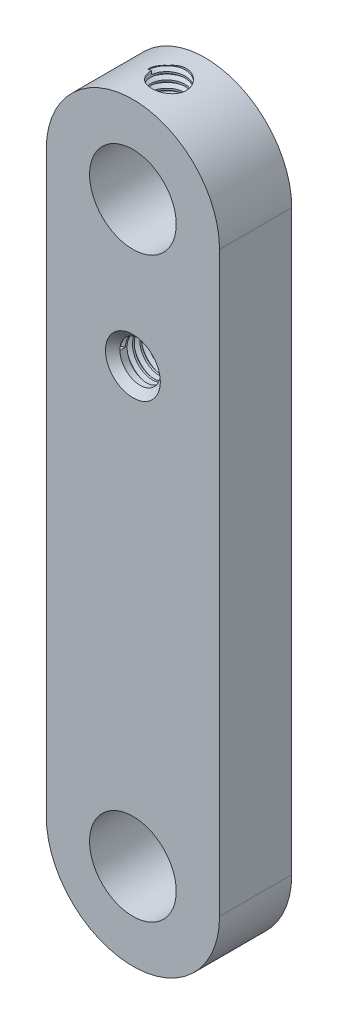
SolidWorks part; units mm, degrees
material "Stop 1060"
ref_plane "Płaszczyzna przednia" through (0, 0, 0) normal (0, 0, 1) x (1, 0, 0)
ref_plane "Płaszczyzna górna" through (0, 0, 0) normal (0, 1, 0) x (1, 0, 0)
ref_plane "Płaszczyzna prawa" through (0, 0, 0) normal (1, 0, 0) x (0, 0, -1)
sketch "Szkic1" plane through (0, 0, 0) normal (0, 0, 1) x (1, 0, 0)
  line L0 (0, 0) -> (0, -40)
  line L1 (6, -40) -> (6, 0)
  line L2 (-6, 0) -> (-6, -40)
  arc A1 (6, 0) -> (-6, 0) centre (0, 0) ccw
  circle A2 centre (0, -40) radius 3
  arc A3 (-6, -40) -> (6, -40) centre (0, -40) ccw
  circle A8 centre (0, -10) radius 1.4
  circle A9 centre (0, 0) radius 3
  dimension "D1" = 6
  dimension "D2" = 12
  dimension "D4" = 6
  dimension "D5" = 12
  dimension "D7" = 2.8
  dimension "D8" = 10
  dimension "D3" = 40
extrude "Dodanie-wyciągnięcie1" add sketch "Szkic1" along normal blind 5 contours L2 A3 L1 A1 A2 region at (0, -45.4663, 0)
chamfer "Sfazowanie1" distance 0.5 angle 45 2 edges at (1.4, -10, 0) (1.4, -10, 5)
thread "Gwint1" pitch 0.5 method cut profile "Profil gwintu1" start angle 0, offset 0, length 10, pitch 0.5, diameter 2.8
ref_plane "Płaszczyzna1" through (-1.4, -10, 4.5) normal (0, -1, 0) x (-1, 0, 0)
sketch "Profil gwintu1" plane through (-1.4, -10, 4.5) normal (0, -1, 0) x (-1, 0, 0)
  line L0 (0, 0) -> (0, 0.5) construction
  line L1 (0, 0) -> (0.2706, 0.1562)
  line L2 (0.2706, 0.1562) -> (0.2706, 0.2187)
  line L3 (0.2706, 0.2187) -> (0, 0.375)
  line L4 (0.2706, 0.1875) -> (0, 0.1875) construction
  line L11 (0, 0) -> (0, 0.375)
  point P2 (0, 0)
  dimension "Pitch" = 0.5
  dimension "Profile_Angle" = 60
  dimension "Profile_Land" = 0.0625
  dimension "Profile_Height" = 0.2706
ref_plane "Płaszczyzna2" through (0, 6, 0) normal (0, 1, 0) x (1, 0, 0)
sketch "Szkic4" plane through (0, 6, 0) normal (0, 1, 0) x (1, 0, 0)
  line L0 (6, -5) -> (6, 0) construction
  line L1 (6, 0) -> (-6, 0) construction
  circle A0 centre (0, -2.5) radius 1.2
  dimension "D1" = 6
  dimension "D2" = 2.5
  dimension "D3" = 2.4
extrude "Wytnij-wyciągnięcie1" cut sketch "Szkic4" against normal up to next
thread "Gwint2" pitch 0.5 method cut profile "Profil gwintu3" start angle 0, offset 0, length 5, pitch 0.5, diameter 2.4
ref_plane "Płaszczyzna4" through (-1.2, 6, 2.5) normal (0, 0, 1) x (-1, 0, 0)
sketch "Profil gwintu3" plane through (-1.2, 6, 2.5) normal (0, 0, 1) x (-1, 0, 0)
  line L0 (0, 0) -> (0, 0.5) construction
  line L1 (0, 0) -> (0.2706, 0.1562)
  line L2 (0.2706, 0.1562) -> (0.2706, 0.2187)
  line L3 (0.2706, 0.2187) -> (0, 0.375)
  line L4 (0.2706, 0.1875) -> (0, 0.1875) construction
  line L11 (0, 0) -> (0, 0.375)
  point P2 (0, 0)
  dimension "Pitch" = 0.5
  dimension "Profile_Angle" = 60
  dimension "Profile_Land" = 0.0625
  dimension "Profile_Height" = 0.2706
